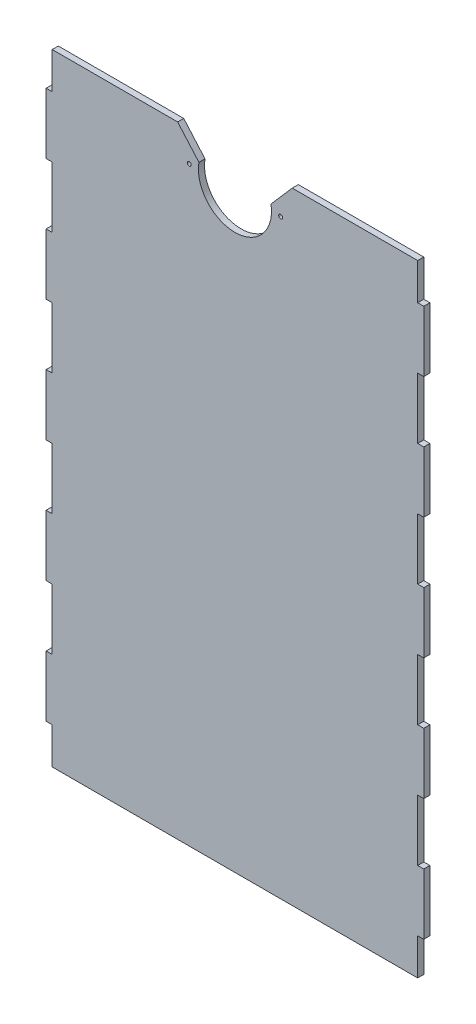
SolidWorks part; units mm, degrees
material "ﾁｰｸ材"
ref_plane "正面" through (0, 0, 0) normal (0, 0, 1) x (1, 0, 0)
ref_plane "平面" through (0, 0, 0) normal (0, 1, 0) x (1, 0, 0)
ref_plane "右側面" through (0, 0, 0) normal (1, 0, 0) x (0, 0, -1)
sketch "ｽｹｯﾁ1" plane through (0, 0, 0) normal (0, 0, 1) x (1, 0, 0)
  line L1 (155, 255) -> (-155, 255)
  line L2 (155, 255) -> (155, -255)
  line L3 (155, -255) -> (-155, -255)
  line L4 (-155, 255) -> (-155, -255)
  line L5 (155, 255) -> (-155, -255) construction
  line L6 (155, -255) -> (-155, 255) construction
  point P0 (0, 0)
  dimension "D1" = 310
  dimension "D2" = 510
extrude "ﾎﾞｽ - 押し出し1" add sketch "ｽｹｯﾁ1" along normal blind 5
sketch "ｽｹｯﾁ2" plane through (0, 0, 5) normal (0, 0, 1) x (1, 0, 0)
  line L0 (155, -255) -> (155, 255) construction
  line L1 (155, 25) -> (150, 25)
  line L2 (155, 25) -> (155, 75)
  line L3 (155, 75) -> (150, 75)
  line L4 (150, 25) -> (150, 75)
  line L9 (155, -75) -> (150, -75)
  line L10 (155, -75) -> (155, -25)
  line L11 (155, -25) -> (150, -25)
  line L12 (150, -75) -> (150, -25)
  line L13 (155, 125) -> (150, 125)
  line L14 (155, 125) -> (155, 175)
  line L15 (155, 175) -> (150, 175)
  line L16 (150, 125) -> (150, 175)
  line L17 (155, -175) -> (150, -175)
  line L18 (155, -175) -> (155, -125)
  line L19 (155, -125) -> (150, -125)
  line L20 (150, -175) -> (150, -125)
  line L21 (155, 225) -> (150, 225)
  line L22 (155, 225) -> (155, 275)
  line L23 (155, 275) -> (150, 275)
  line L24 (150, 225) -> (150, 275)
  line L25 (155, -275) -> (150, -275)
  line L26 (155, -275) -> (155, -225)
  line L27 (155, -225) -> (150, -225)
  line L28 (150, -275) -> (150, -225)
  line L29 (-150, 25) -> (-155, 25)
  line L30 (-150, 25) -> (-150, 75)
  line L31 (-150, 75) -> (-155, 75)
  line L32 (-155, 25) -> (-155, 75)
  line L33 (-150, -75) -> (-155, -75)
  line L34 (-150, -75) -> (-150, -25)
  line L35 (-150, -25) -> (-155, -25)
  line L36 (-155, -75) -> (-155, -25)
  line L37 (-150, 125) -> (-155, 125)
  line L38 (-150, 125) -> (-150, 175)
  line L39 (-150, 175) -> (-155, 175)
  line L40 (-155, 125) -> (-155, 175)
  line L41 (-150, -175) -> (-155, -175)
  line L42 (-150, -175) -> (-150, -125)
  line L43 (-150, -125) -> (-155, -125)
  line L44 (-155, -175) -> (-155, -125)
  line L45 (-150, 225) -> (-155, 225)
  line L46 (-150, 225) -> (-150, 275)
  line L47 (-150, 275) -> (-155, 275)
  line L48 (-155, 225) -> (-155, 275)
  line L49 (-150, -275) -> (-155, -275)
  line L50 (-150, -275) -> (-150, -225)
  line L51 (-150, -225) -> (-155, -225)
  line L52 (-155, -275) -> (-155, -225)
  line L53 (-155, 255) -> (-155, -255) construction
  point P53 (-152.5, 25)
  dimension "D1" = 5
  dimension "D2" = 50
  dimension "D3" = 25
  dimension "D4" = 50
  dimension "D5" = 50
  dimension "D6" = 50
  dimension "D7" = 50
  dimension "D8" = 50
  dimension "D9" = 5
  dimension "D10" = 50
  dimension "D11" = 50
  dimension "D12" = 50
  dimension "D13" = 50
  dimension "D14" = 50
  dimension "D15" = 50
  dimension "D16" = 25
extrude "ｶｯﾄ - 押し出し1" cut sketch "ｽｹｯﾁ2" against normal blind 5
sketch "ｽｹｯﾁ3" plane through (0, 0, 5) normal (0, 0, 1) x (1, 0, 0)
  line L0 (47.0333, 255) -> (29.5804, 235)
  line L2 (150, 255) -> (-150, 255) construction
  line L3 (47.0333, 255) -> (-47.0333, 255)
  line L4 (-47.0333, 255) -> (-29.5804, 235)
  arc A1 (29.5804, 235) -> (-29.5804, 235) centre (0, 230) cw
  dimension "D1" = 30
  dimension "D2" = 25
  dimension "D3" = 19
  dimension "D4" = 19
  dimension "D5" = 5
  dimension "D6" = 5
extrude "ｶｯﾄ - 押し出し2" cut sketch "ｽｹｯﾁ3" against normal through all
sketch "ｽｹｯﾁ5" plane through (0, 0, 5) normal (0, 0, 1) x (1, 0, 0)
  circle A0 centre (-37.5, 230) radius 1.6
  circle A1 centre (37.5, 230) radius 1.6
  point P4 (0, 230)
  point P5 (37.1668, 225.0118)
  dimension "D1" = 3.2
  dimension "D2" = 37.5
  dimension "D3" = 37.5
extrude "ｶｯﾄ - 押し出し3" cut sketch "ｽｹｯﾁ5" against normal through all
